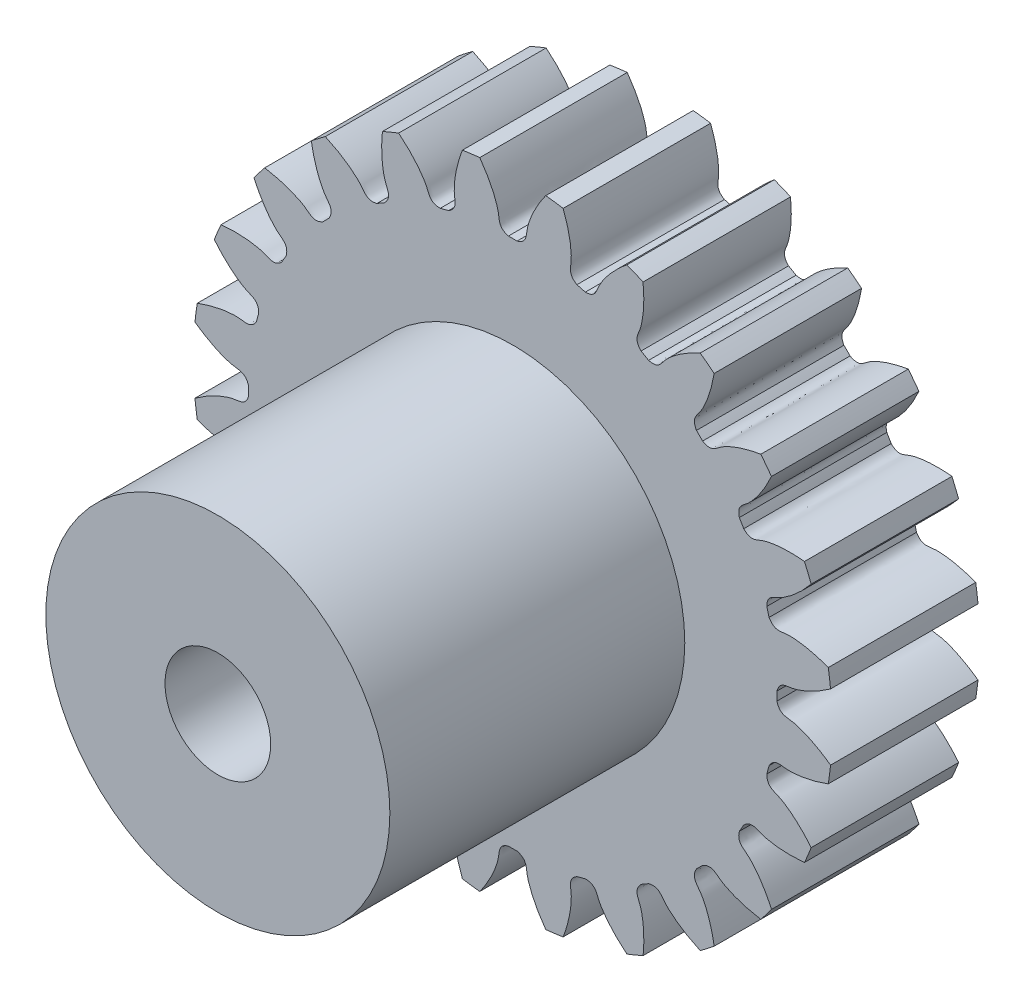
SolidWorks part; units mm, degrees
ref_plane "前视基准面" through (0, 0, 0) normal (0, 0, 1) x (1, 0, 0)
ref_plane "上视基准面" through (0, 0, 0) normal (0, 1, 0) x (1, 0, 0)
ref_plane "右视基准面" through (0, 0, 0) normal (1, 0, 0) x (0, 0, -1)
other "Configuration Table"
sketch "草图1" plane through (0, 0, 0) normal (0, 0, 1) x (1, 0, 0)
  circle A0 centre (0, 0) radius 6.5
extrude "凸台-拉伸1" add sketch "草图1" along normal blind 3
ref_axis "基准轴1" through (0, 0, 3) along (0, 0, -1)
sketch "草图2" plane through (0, 0, 0) normal (0, 0, 1) x (1, 0, 0)
  line L0 (0, 0) -> (0, 6.5) construction
  circle A0 centre (0, 0) radius 6.5 construction
  arc A1 (0.0884, 5.3743) -> (-0.0884, 5.3743) centre (0, 0) ccw
  arc A2 (1.5578, 7.3471) -> (-1.5578, 7.3471) centre (0, 0) ccw
  spline S0 degree 3 poles (0.0884, 5.3743) (0.284, 5.4284) (0.2695, 5.5579) (0.2931, 5.6863) (0.2965, 5.7029) (0.3007, 5.7216) (0.3058, 5.7424) (0.312, 5.7653) (0.3191, 5.7902) (0.3275, 5.8171) (0.3371, 5.846) (0.348, 5.8769) (0.3604, 5.9096) (0.3742, 5.9441) (0.3896, 5.9805) (0.4067, 6.0185) (0.4254, 6.0583) (0.446, 6.0997) (0.4684, 6.1427) (0.4928, 6.1872) (0.5192, 6.2332) (0.5476, 6.2806) (0.5782, 6.3293) (0.611, 6.3792) (0.6461, 6.4304) (0.6834, 6.4827) (0.7232, 6.536) (0.7654, 6.5903) (0.8101, 6.6456) (0.8574, 6.7016) (0.9073, 6.7583) (0.9598, 6.8158) (1.015, 6.8738) (1.0729, 6.9322) (1.1336, 6.9911) (1.1972, 7.0503) (1.2635, 7.1097) (1.3328, 7.1693) (1.4302, 7.2497) (1.506, 7.3084) (1.5578, 7.3471) knots 0 0 0 0 0.143961 0.149818 0.156577 0.164236 0.172796 0.182258 0.19262 0.203884 0.216049 0.229115 0.243082 0.25795 0.273719 0.290389 0.30796 0.326433 0.345806 0.366081 0.387257 0.409333 0.432311 0.45619 0.48097 0.506651 0.533234 0.560717 0.589101 0.618387 0.648574 0.679661 0.71165 0.74454 0.778331 0.813023 0.848616 0.885111 0.922506 1 1 1 1
  spline S1 degree 3 poles (-0.0884, 5.3743) (-0.284, 5.4284) (-0.2695, 5.5579) (-0.2931, 5.6863) (-0.2965, 5.7029) (-0.3007, 5.7216) (-0.3058, 5.7424) (-0.312, 5.7653) (-0.3191, 5.7902) (-0.3275, 5.8171) (-0.3371, 5.846) (-0.348, 5.8769) (-0.3604, 5.9096) (-0.3742, 5.9441) (-0.3896, 5.9805) (-0.4067, 6.0185) (-0.4254, 6.0583) (-0.446, 6.0997) (-0.4684, 6.1427) (-0.4928, 6.1872) (-0.5192, 6.2332) (-0.5476, 6.2806) (-0.5782, 6.3293) (-0.611, 6.3792) (-0.6461, 6.4304) (-0.6834, 6.4827) (-0.7232, 6.536) (-0.7654, 6.5903) (-0.8101, 6.6456) (-0.8574, 6.7016) (-0.9073, 6.7583) (-0.9598, 6.8158) (-1.015, 6.8738) (-1.0729, 6.9322) (-1.1336, 6.9911) (-1.1972, 7.0503) (-1.2635, 7.1097) (-1.3328, 7.1693) (-1.4302, 7.2497) (-1.506, 7.3084) (-1.5578, 7.3471) knots 0 0 0 0 0.143961 0.149818 0.156577 0.164236 0.172796 0.182258 0.19262 0.203884 0.216049 0.229115 0.243082 0.25795 0.273719 0.290389 0.30796 0.326433 0.345806 0.366081 0.387257 0.409333 0.432311 0.45619 0.48097 0.506651 0.533234 0.560717 0.589101 0.618387 0.648574 0.679661 0.71165 0.74454 0.778331 0.813023 0.848616 0.885111 0.922506 1 1 1 1
extrude "切除-拉伸1" cut sketch "草图2" along normal through all
pattern_circular "阵列(圆周)1" count 24 every 15 about axis through (0, 0, 3) along (0, 0, -1) of "切除-拉伸1"
sketch "草图3" plane through (0, 0, 0) normal (0, 0, 1) x (1, 0, 0)
  circle A0 centre (0, 0) radius 6 construction
  dimension "Dn" = 12
sketch "草图5" plane through (0, 0, 3) normal (0, 0, 1) x (1, 0, 0)
  circle A0 centre (0, 0) radius 3.5
  dimension "D1" = 7
extrude "凸台-拉伸2" add sketch "草图5" along normal blind 6
sketch "草图4" plane through (0, 0, 3) normal (0, 0, 1) x (1, 0, 0)
  circle A0 centre (0, 0) radius 1.075
  dimension "D1" = 2.15
extrude "切除-拉伸2" cut sketch "草图4" along normal up to next from surface starting at face at (0, 0, 0)
